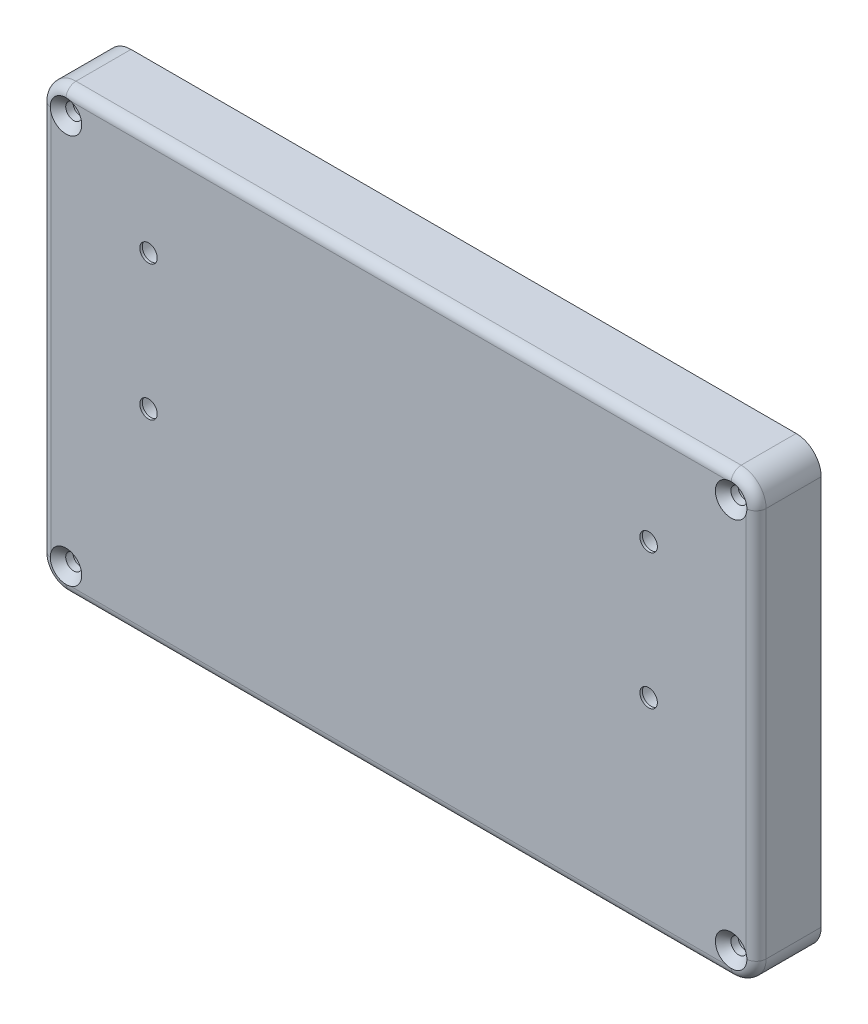
SolidWorks part; units mm, degrees
ref_plane "Front Plane" through (0, 0, 0) normal (0, 0, 1) x (1, 0, 0)
ref_plane "Top Plane" through (0, 0, 0) normal (0, 1, 0) x (1, 0, 0)
ref_plane "Right Plane" through (0, 0, 0) normal (1, 0, 0) x (0, 0, -1)
sketch "Sketch1" plane through (0, 0, 0) normal (0, 0, 1) x (1, 0, 0)
  line L0 (12.5, 41) -> (12.5, -41) construction
  line L1 (-71.5, 44) -> (71.5, 44) construction
  line L2 (-71.5, 44) -> (-71.5, -44) construction
  line L3 (-71.5, -44) -> (71.5, -44) construction
  line L4 (71.5, 44) -> (71.5, -44) construction
  line L5 (-71.5, 44) -> (71.5, -44) construction
  line L6 (-71.5, -44) -> (71.5, 44) construction
  line L7 (-48.5, 31) -> (-0.5, 31) construction
  line L8 (-48.5, 31) -> (-48.5, -28) construction
  line L9 (-48.5, -28) -> (-0.5, -28) construction
  line L10 (-0.5, 31) -> (-0.5, -28) construction
  line L11 (-48.5, 31) -> (-0.5, -28) construction
  line L12 (-48.5, -28) -> (-0.5, 31) construction
  line L13 (-68.5, 41) -> (68.5, 41) construction
  line L14 (-68.5, 41) -> (-68.5, -41) construction
  line L15 (-68.5, -41) -> (68.5, -41) construction
  line L16 (68.5, 41) -> (68.5, -41) construction
  line L17 (-68.5, 41) -> (68.5, -41) construction
  line L18 (-68.5, -41) -> (68.5, 41) construction
  line L19 (15.5, 41) -> (15.5, -41) construction
  line L20 (15.5, -14) -> (68.5, -14) construction
  line L21 (-66.5, 44) -> (66.5, 44)
  line L22 (27.25, 32.25) -> (59.75, 32.25) construction
  line L23 (27.25, 32.25) -> (27.25, -0.25) construction
  line L24 (27.25, -0.25) -> (59.75, -0.25) construction
  line L25 (59.75, 32.25) -> (59.75, -0.25) construction
  line L26 (27.25, 32.25) -> (59.75, -0.25) construction
  line L27 (27.25, -0.25) -> (59.75, 32.25) construction
  line L28 (71.5, 39) -> (71.5, -39)
  line L29 (-71.5, 39) -> (-71.5, -39)
  line L31 (-66.5, -44) -> (66.5, -44)
  circle A0 centre (43.5, 16) radius 19.75 construction
  circle A1 centre (27.25, 32.25) radius 1.25 construction
  circle A2 centre (59.75, 32.25) radius 1.25 construction
  circle A3 centre (59.75, -0.25) radius 1.25 construction
  circle A4 centre (27.25, -0.25) radius 1.25 construction
  arc A5 (66.5, -44) -> (71.5, -39) centre (66.5, -39) ccw
  arc A6 (66.5, 44) -> (71.5, 39) centre (66.5, 39) cw
  arc A7 (-66.5, 44) -> (-71.5, 39) centre (-66.5, 39) ccw
  arc A8 (-71.5, -39) -> (-66.5, -44) centre (-66.5, -39) ccw
  point P0 (0, 0)
  point P6 (-24.5, 1.5)
  point P13 (0, 0)
  dimension "D11" = 39.5
  dimension "D16" = 2.5
  dimension "D17" = 5
  dimension "D1" = 143
  dimension "D2" = 13
  dimension "D3" = 48
  dimension "D4" = 59
  dimension "D5" = 3
  dimension "D6" = 3
  dimension "D7" = 10
  dimension "D8" = 20
  dimension "D9" = 3
  dimension "D10" = 13
  dimension "D12" = 28
  dimension "D13" = 25
  dimension "D14" = 30
  dimension "D15" = 32.5
extrude "Boss-Extrude1" add sketch "Sketch1" along normal blind 3
sketch "Sketch2" plane through (0, 0, 0) normal (0, 0, -1) x (-1, 0, 0)
  line L0 (-66.5, 44) -> (66.5, 44)
  line L1 (71.5, 39) -> (71.5, -39)
  line L2 (66.5, -44) -> (-66.5, -44)
  line L3 (-71.5, 39) -> (-71.5, -39)
  line L4 (0, 44) -> (0, -44) construction
  line L5 (-71.5, 0) -> (71.5, 0) construction
  line L6 (-61.9174, 41) -> (61.9174, 41)
  line L7 (-68.5, 34.4174) -> (-68.5, -34.4174)
  line L8 (68.5, 34.4174) -> (68.5, -34.4174)
  line L9 (-61.9174, -41) -> (61.9174, -41)
  line L10 (61.9174, -41) -> (61.9174, -37)
  line L11 (61.9174, 41) -> (61.9174, 37)
  arc A0 (-71.5, 39) -> (-66.5, 44) centre (-66.5, 39) cw
  arc A1 (66.5, 44) -> (71.5, 39) centre (66.5, 39) cw
  arc A2 (71.5, -39) -> (66.5, -44) centre (66.5, -39) cw
  arc A3 (-66.5, -44) -> (-71.5, -39) centre (-66.5, -39) cw
  circle A4 centre (-66.5, 39) radius 5 construction
  arc A5 (61.9174, 37) -> (61.9174, 41) centre (66.5, 39) ccw construction
  arc A6 (61.9174, -41) -> (61.9174, -37) centre (66.5, -39) ccw construction
  circle A7 centre (-66.5, -39) radius 5 construction
  arc A8 (-68.5, 34.4174) -> (-61.9174, 41) centre (-66.5, 39) ccw
  circle A9 centre (-66.5, 39) radius 2
  circle A10 centre (66.5, 39) radius 2
  arc A11 (68.5, 34.4174) -> (61.9174, 37) centre (66.5, 39) cw
  arc A12 (68.5, -34.4174) -> (61.9174, -37) centre (66.5, -39) ccw
  circle A13 centre (66.5, -39) radius 2
  circle A14 centre (-66.5, -39) radius 2
  arc A15 (-68.5, -34.4174) -> (-61.9174, -41) centre (-66.5, -39) cw
  point P38 (0, 41)
  point P39 (68.5, 0)
  point P44 (-68.5, 0)
  dimension "D3" = 4
  dimension "D1" = 3
  dimension "D2" = 3
extrude "Boss-Extrude2" add sketch "Sketch2" along normal blind 10
fillet "Fillet2" radius 2 12 edges at (-70.0355, 42.5355, 3) (0, 44, 3) (70.0355, 42.5355, 3) (71.5, 0, 3) (70.0355, -42.5355, 3) (0, -44, 3) (-70.0355, -42.5355, 3) (0, -41, 0) (-68.5, 0, 0) (0, 41, 0) (68.5, 0, 0) (-71.5, 0, 3)
hole_wizard "CSK for M3 Flat Head Machine Screw1" positions "Sketch3" profile "Sketch4" countersink size "M3" standard "ANSI Metric" end condition through all
sketch "Sketch3" plane through (0, 0, 3) normal (0, 0, 1) x (1, 0, 0)
  point P0 (-66.5, 39)
  point P3 (66.5, 39)
  point P6 (66.5, -39)
  point P9 (-66.5, -39)
sketch "Sketch4" plane through (-66.5, 39, 3) normal (1, 0, 0) x (0, -1, 0)
  line L0 (0, 0) -> (0, 13)
  line L1 (0, 13) -> (1.6, 13)
  line L2 (1.6, 13) -> (1.6, 1.55)
  line L3 (1.6, 1.55) -> (3.15, 0)
  line L5 (3.15, 0) -> (0, 0)
  line L6 (-1.6, 1.55) -> (-3.15, 0) construction
  line L11 (0, -6.35) -> (0, 107.95) construction
  dimension "Thru Hole Dia." = 3.2
  dimension "Thru Hole Depth" = 13
  dimension "Near C'Sink Dia." = 6.3
  dimension "Near C'Sink Angle" = 90
sketch "Sketch5" plane through (0, 0, -10) normal (0, 0, -1) x (-1, 0, 0)
  line L0 (61.9174, 41) -> (-61.9174, 41) construction
  line L1 (-56.5, 41) -> (56.5, 41)
  line L2 (-56.5, 41) -> (-56.5, 39)
  line L3 (-56.5, 39) -> (56.5, 39)
  line L4 (56.5, 41) -> (56.5, 39)
  line L5 (61.9174, 39) -> (-61.5, 39) construction
  line L6 (-68.5, 34.4174) -> (-68.5, -34.4174) construction
  line L7 (-68.5, 29) -> (-66.5, 29)
  line L8 (-68.5, 29) -> (-68.5, -29)
  line L9 (-68.5, -29) -> (-66.5, -29)
  line L10 (-66.5, 29) -> (-66.5, -29)
  line L11 (-66.5, 34) -> (-66.5, -34) construction
  line L12 (-61.5, -39) -> (61.9174, -39) construction
  line L13 (-56.5, -39) -> (56.5, -39)
  line L14 (-56.5, -39) -> (-56.5, -41)
  line L15 (-56.5, -41) -> (56.5, -41)
  line L16 (56.5, -39) -> (56.5, -41)
  line L17 (-61.9174, -41) -> (61.9174, -41) construction
  line L18 (68.5, -34.4174) -> (68.5, 34.4174) construction
  line L19 (68.5, -29) -> (66.5, -29)
  line L20 (68.5, -29) -> (68.5, 29)
  line L21 (68.5, 29) -> (66.5, 29)
  line L22 (66.5, -29) -> (66.5, 29)
  line L23 (66.5, -34) -> (66.5, 34) construction
  line L24 (-71.5, 39) -> (-71.5, -39) construction
  line L25 (71.5, -39) -> (71.5, 39) construction
  line L26 (66.5, 44) -> (-66.5, 44) construction
  line L27 (-66.5, -44) -> (66.5, -44) construction
  point P40 (0, 0)
  point P41 (0, 0)
  point P42 (0, 0)
  point P43 (0, 0)
  dimension "D1" = 15
  dimension "D2" = 15
  dimension "D3" = 15
  dimension "D5" = 15
extrude "Boss-Extrude3" add sketch "Sketch5" along normal blind 2 and the other way blind 4
chamfer "Chamfer1" distance 2 angle 45 4 edges at (0, -39, -6) (-66.5, 0, -6) (66.5, 0, -6) (0, 39, -6)
chamfer "Chamfer2" distance 0.5 angle 45 4 edges at (-68.5, 0, -12) (0, 41, -12) (0, -41, -12) (68.5, 0, -12)
sketch "Sketch6" plane through (0, 0, 3) normal (0, 0, 1) x (1, 0, 0)
  line L1 (-50, 23.5) -> (50, 23.5) construction
  line L2 (-50, 23.5) -> (-50, -3.5) construction
  line L3 (-50, -3.5) -> (50, -3.5) construction
  line L4 (50, 23.5) -> (50, -3.5) construction
  line L5 (-50, 23.5) -> (50, -3.5) construction
  line L6 (-50, -3.5) -> (50, 23.5) construction
  circle A0 centre (-50, 23.5) radius 1.75
  circle A1 centre (-50, -3.5) radius 1.75
  circle A2 centre (50, -3.5) radius 1.75
  circle A3 centre (50, 23.5) radius 1.75
  point P0 (0, 10)
  point P9 (0, 0)
  dimension "D3" = 3.5
  dimension "D1" = 100
  dimension "D2" = 27
  dimension "D4" = 10
extrude "Cut-Extrude1" cut sketch "Sketch6" against normal through all
sketch "Sketch7" plane through (0, 0, 0) normal (0, 0, -1) x (-1, 0, 0)
  circle A0 centre (-50, 23.5) radius 4
  circle A1 centre (-50, 23.5) radius 2.75
  circle A2 centre (-50, -3.5) radius 4
  circle A3 centre (-50, -3.5) radius 2.75
  circle A4 centre (50, -3.5) radius 4
  circle A5 centre (50, -3.5) radius 2.75
  circle A6 centre (50, 23.5) radius 4
  circle A7 centre (50, 23.5) radius 2.75
  dimension "D1" = 8
  dimension "D2" = 5.5
extrude "Boss-Extrude4" add sketch "Sketch7" along normal blind 1.5
sketch "Sketch8" plane through (0, 0, -1.5) normal (0, 0, -1) x (-1, 0, 0)
  circle A0 centre (-50, 23.5) radius 2.75
  circle A1 centre (-50, -3.5) radius 2.75
  circle A2 centre (50, -3.5) radius 2.75
  circle A3 centre (50, 23.5) radius 2.75
  circle A4 centre (-50, 23.5) radius 2.75 construction
extrude "Cut-Extrude2" cut sketch "Sketch8" against normal blind 4
